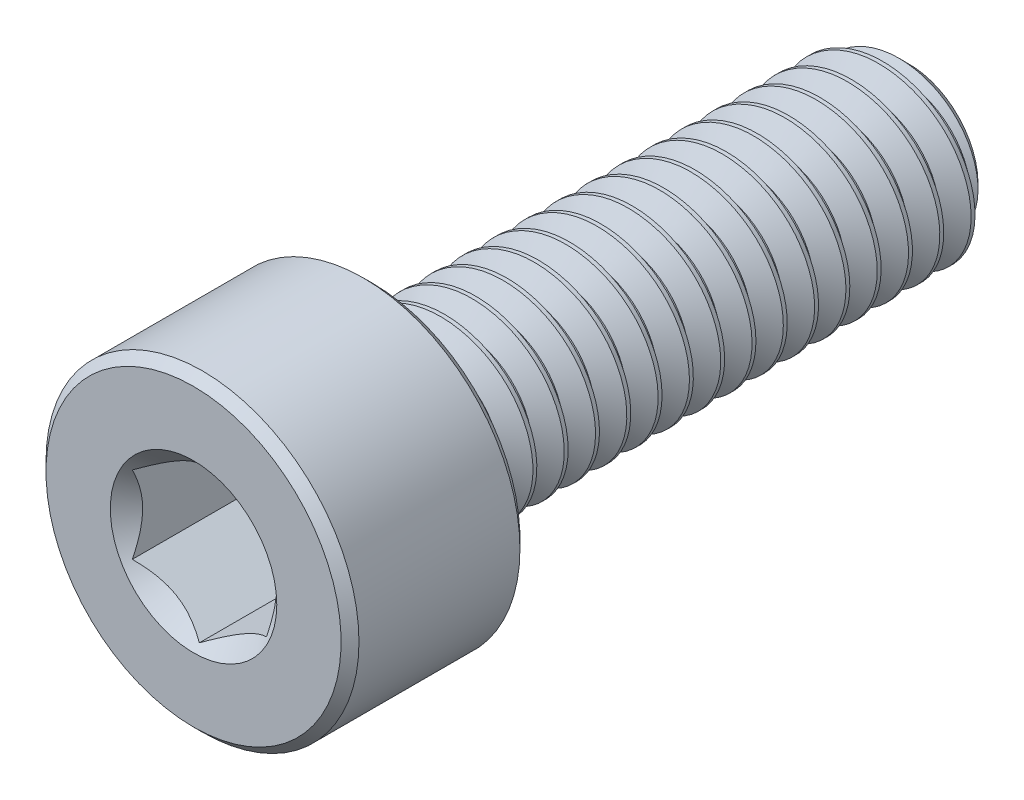
SolidWorks part; units mm, degrees
ref_plane "Front Plane" through (0, 0, 0) normal (0, 0, 1) x (1, 0, 0)
ref_plane "Top Plane" through (0, 0, 0) normal (0, 1, 0) x (1, 0, 0)
ref_plane "Right Plane" through (0, 0, 0) normal (1, 0, 0) x (0, 0, -1)
sketch "Sketch1" plane through (0, 0, 0) normal (1, 0, 0) x (0, 0, -1)
  line L0 (-8, 0) -> (8, 0) construction
  line L1 (8, 0) -> (8, 1.5453) construction
  line L2 (8, 1.5453) -> (7.5453, 2) construction
  line L3 (7.5453, 2) -> (7.475, 2) construction
  line L4 (7.475, 2) -> (-4, 2) construction
  line L5 (-4, 2) -> (-4, 3.5) construction
  line L6 (-4, 3.5) -> (-8, 3.5) construction
  line L7 (-8, 3.5) -> (-8, 0) construction
  line L8 (8, 1.5453) -> (8, 2) construction
  line L9 (7.9562, 2.0758) -> (8.3062, 1.4696) construction
  line L10 (8.3062, 1.4696) -> (8.6562, 2.0758) construction
  line L11 (8.6562, 2.0758) -> (7.9562, 2.0758) construction
  line L12 (8.3062, 2.0758) -> (8.3062, 2) construction
  line L13 (8.3062, 1.4696) -> (8.3062, 1.5453) construction
  line L14 (8.2625, 1.5453) -> (8.35, 1.5453) construction
  line L15 (8, 2) -> (8.6125, 2) construction
  line L16 (7.9781, 2.0379) -> (8.6344, 2.0379) construction
  line L17 (8, 0) -> (8, -2) construction
  line L18 (-4.2, 3.5) -> (-4, 3.3) construction
  line L19 (-7.8, 3.5) -> (-8, 3.3) construction
  line L20 (-4, 2) -> (-4, 0) construction
  line L21 (-4, 1) -> (0, 1) construction
  line L22 (0, 1) -> (4, 1) construction
  line L23 (4, 1) -> (8, 1) construction
  line L24 (0, 1) -> (0, 2) construction
  line L25 (0, 2) -> (0, 3.5) construction
  line L26 (4, 1) -> (4, 3.5) construction
  point P0 (-8, 1.5)
  point P3 (6.25, 2)
  point P4 (0, 0)
  point P18 (4, 2)
  point P22 (8.3062, 1.5453)
  point P24 (7.475, 2)
  point P25 (8.3062, 2)
  point P28 (8.3062, 2.0379)
  point P29 (6.25, -2)
  point P30 (0, 2)
  point P31 (-6, 3.5)
  point P37 (-4.7, 3.5)
  point P38 (-7.7, 3.5)
  point P45 (0, 1)
  point P46 (4, 1)
  dimension "D2" = 0.0875
  dimension "D7" = 0.2
  dimension "D8" = 0.2
  dimension "D9" = 0.2
  dimension "D10" = 0.1
  dimension "D11" = 0.5
  dimension "Drive Size" = 3
  dimension "Head Diameter" = 7
  dimension "Head Height" = 4
  dimension "Thread Pitch" = 0.7
  dimension "Thread Dia" = 4
  dimension "Length" = 12
  dimension "D12" = 0.525
  dimension "D4" = 1.75
  dimension "D3" = 45
sketch "Sketch2" plane through (0, 0, 0) normal (1, 0, 0) x (0, 0, -1)
  line L0 (-8, 0) -> (-8, 3.3)
  line L1 (-7.8, 3.5) -> (-4.2, 3.5)
  line L2 (-4, 3.3) -> (-4, 2.2)
  line L4 (7.5453, 2) -> (8, 1.5453)
  line L5 (8, 1.5453) -> (8, 0)
  line L6 (-4, 3.5) -> (-8, 3.5) construction
  line L7 (8, 0) -> (-8, 0)
  line L8 (-7.8, 3.5) -> (-8, 3.3) construction
  line L10 (-7.8, 3.5) -> (-8, 3.3)
  line L14 (-4.2, 3.5) -> (-4, 3.3) construction
  line L16 (-4.2, 3.5) -> (-4, 3.3)
  line L17 (-4, 2) -> (-4, 3.5) construction
  line L19 (-3.8, 2) -> (7.5453, 2)
  line L20 (7.475, 2) -> (-4, 2) construction
  arc A1 (-4, 2.2) -> (-3.8, 2) centre (-3.8, 2.2) ccw
  dimension "D3" = 0.2
revolve "Revolve1" add sketch "Sketch2" angle 360 about L7
sketch "Sketch3" plane through (0, 0, 8) normal (0, 0, 1) x (1, 0, 0)
  line L1 (1.5, -0.866) -> (1.5, 0.866)
  line L2 (1.5, 0.866) -> (0, 1.7321)
  line L3 (0, 1.7321) -> (-1.5, 0.866)
  line L4 (-1.5, 0.866) -> (-1.5, -0.866)
  line L5 (-1.5, -0.866) -> (0, -1.7321)
  line L6 (0, -1.7321) -> (1.5, -0.866)
  circle A0 centre (0, 0) radius 1.5 construction
  circle A1 centre (0, 0) radius 3.5 construction
  circle A2 centre (0, 0) radius 3.5 construction
  circle A3 centre (0, 0) radius 1.7321 construction
  point P13 (0, 0)
  dimension "D1" = 3.4641
extrude "Cut-Extrude1" cut sketch "Sketch3" against normal offset from surface (3 mm away) 1 up to face at (0, 3.3, 4)
sketch "Sketch4" plane through (0, 0, 8) normal (0, 0, 1) x (1, 0, 0)
  circle A0 centre (0, 0) radius 1.862
  dimension "D1" = 3.7239
extrude "Cut-Extrude2" cut sketch "Sketch4" against normal up to vertex (2 mm away) draft 45 up to point (0, 3.5, 6)
sketch "Sketch11" plane through (0, 0, 0) normal (1, 0, 0) x (0, 0, -1)
  line L0 (-8, 0) -> (8, 0) construction
  line L1 (-8, 0) -> (8, 0) construction
  line L2 (-1.75, 0) -> (-1.75, 2) construction
  line L3 (7.475, 2) -> (-4, 2) construction
  line L4 (5.75, 0) -> (5.75, 2) construction
  line L6 (8, 1.5453) -> (8, 2) construction
  point P2 (-1.75, 0)
  point P3 (5.75, 0)
  dimension "D1" = 2.25
  dimension "D2" = 2.25
sketch "Sketch6" plane through (0, 0, -8) normal (0, 0, -1) x (-1, 0, 0)
  circle A0 centre (0, 0) radius 2
curve "Helix/Spiral1" pitch 0.7 height 12.7 turns 18.1429
sketch "Sketch10" plane through (0, 0, 0) normal (1, 0, 0) x (0, 0, -1)
  line L0 (-3.8, -3.5) -> (-3.8, 3.5)
  line L5 (-8, 0) -> (8, 0) construction
  line L6 (-3.8, 2) -> (-3.8, -2) construction
  point P3 (-3.8, 0)
split "Split1" trim tools "Sketch10" bodies to split 106 resulting bodies 114 115
sketch "Sketch7" plane through (0, 0, 0) normal (1, 0, 0) x (0, 0, -1)
  line L0 (7.9781, 2.0379) -> (8.6344, 2.0379)
  line L1 (8.6344, 2.0379) -> (8.35, 1.5453)
  line L2 (8.35, 1.5453) -> (8.2625, 1.5453)
  line L3 (8.2625, 1.5453) -> (7.9781, 2.0379)
sweep "Cut-Sweep1" cut profiles "Sketch7" path "Helix/Spiral1"
sketch "Sketch8" plane through (0, 0, 0) normal (1, 0, 0) x (0, 0, -1)
  line L0 (-4, 0) -> (-4, 2)
  line L1 (-3.8, -2) -> (-3.8, 2) construction
  line L2 (-4, 2) -> (-3.8, 2)
  line L4 (-3.8, 2) -> (-2.6453, 0)
  line L5 (-2.6453, 0) -> (-4, 0)
  line L6 (7.475, 2) -> (-4, 2) construction
  line L7 (-8, 0) -> (8, 0) construction
  dimension "D1" = 60
revolve "Revolve2" add sketch "Sketch8" angle 360 about L5
equation "\"D2@Sketch1\" = \"Thread Pitch@Sketch1\" / 8"
equation "\"D4@Helix/Spiral1\" = \"Thread Pitch@Sketch1\""
equation "\"D7@Sketch1\" = \"Head Height@Sketch1\" * .05"
equation "\"D8@Sketch1\"=\"D7@Sketch1\""
equation "\"D9@Sketch1\"=\"D7@Sketch1\""
equation "\"D10@Sketch1\"=\"D7@Sketch1\"/2"
equation "\"D11@Sketch1\"=\"D10@Sketch1\"*5"
equation "\"D4@Sketch1\"=\"Thread Pitch@Sketch1\"*2.5"
equation "\"D12@Sketch1\"=\"Thread Pitch@Sketch1\"*.75"
equation "\"D3@Helix/Spiral1\"=\"Length@Sketch1\"+\"Thread Pitch@Sketch1\""
equation "\"D3@Sketch2\"=\"Thread Dia@Sketch1\"*0.05"
equation "\"D1@Sketch11\"=\"Length@Sketch1\"*0.1875"
equation "\"D2@Sketch11\"=\"D1@Sketch11\""
equation "\"D1@Sketch4\"=\"D1@Sketch3\"*1.075"
